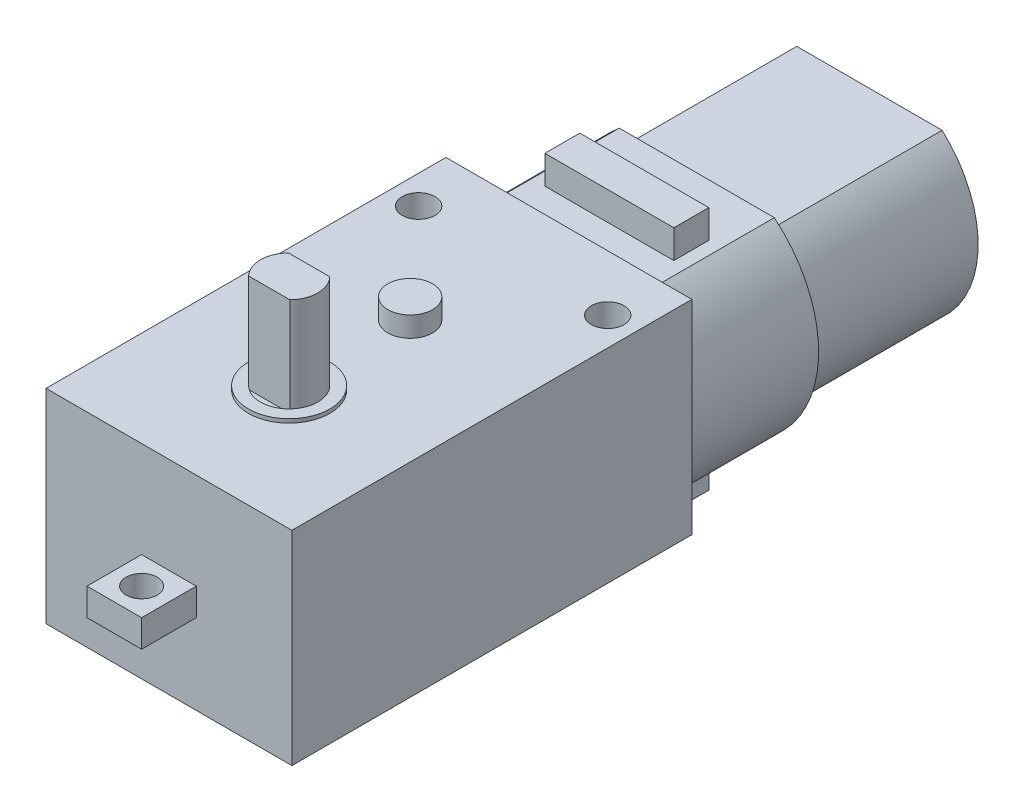
SolidWorks part; units mm, degrees
ref_plane "Front Plane" through (0, 0, 0) normal (0, 0, 1) x (1, 0, 0)
ref_plane "Top Plane" through (0, 0, 0) normal (0, 1, 0) x (1, 0, 0)
ref_plane "Right Plane" through (0, 0, 0) normal (1, 0, 0) x (0, 0, -1)
sketch "Sketch1" plane through (0, 0, 0) normal (0, 1, 0) x (1, 0, 0)
  line L0 (0, -3.725) -> (0, 13.125) construction
  line L1 (-11.25, -11) -> (11.25, -11)
  line L2 (-11.25, -11) -> (-11.25, 25.6)
  line L3 (-11.25, 25.6) -> (11.25, 25.6)
  line L4 (11.25, -11) -> (11.25, 25.6)
  line L5 (-11.25, -11) -> (11.25, 25.6) construction
  line L6 (-11.25, 25.6) -> (11.25, -11) construction
  line L8 (-11.15, 37.3) -> (11.15, 37.3)
  line L9 (-11.15, 37.3) -> (-11.15, 25.6)
  line L10 (-11.15, 25.6) -> (11.15, 25.6)
  line L11 (11.15, 37.3) -> (11.15, 25.6)
  line L12 (-11.15, 37.3) -> (11.15, 25.6) construction
  line L13 (-11.15, 25.6) -> (11.15, 37.3) construction
  line L14 (-9.7, 53.3) -> (9.7, 53.3)
  line L15 (-9.7, 53.3) -> (-9.7, 37.3)
  line L16 (-9.7, 37.3) -> (9.7, 37.3)
  line L17 (9.7, 53.3) -> (9.7, 37.3)
  line L18 (-9.7, 53.3) -> (9.7, 37.3) construction
  line L19 (-9.7, 37.3) -> (9.7, 53.3) construction
  line L26 (-1.8868, -1.825) -> (1.8868, -1.825)
  line L28 (-1.8868, 1.825) -> (1.8868, 1.825)
  line L30 (-1.8868, -1.825) -> (1.8868, 1.825) construction
  line L31 (-1.8868, 1.825) -> (1.8868, -1.825) construction
  circle A0 centre (0, 0) radius 3.725
  circle A1 centre (0, 11.075) radius 2.05
  circle A2 centre (0, 0) radius 2.625
  point P0 (0, 7.3)
  point P12 (0, 31.45)
  point P17 (0, 45.3)
  point P22 (0, 30.9)
  dimension "D3" = 11
  dimension "D4" = 7.45
  dimension "D5" = 16.85
  dimension "D6" = 4.1
  dimension "D14" = 5.25
  dimension "D1" = 36.6
  dimension "D2" = 22.5
  dimension "D7" = 22.3
  dimension "D8" = 19.4
  dimension "D9" = 11.7
  dimension "D10" = 16
  dimension "D15" = 3.65
extrude "Boss-Extrude1" add sketch "Sketch1" against normal blind 18.65 contours L4 L3 L2 L1
ref_plane "Plane2" through (0, -18.65, 0) normal (0, -1, 0) x (-1, 0, 0)
extrude "Boss-Extrude2" add sketch "Sketch1<3>" along normal blind 17.2 from surface contours L8 L11 L10 L9 starting at plane "Plane2"
sketch "Sketch1<3>" plane through (0, 0, 0) normal (0, 1, 0) x (1, 0, 0) same geometry as "Sketch1"
sketch "Sketch3" plane through (0, 0, -25.6) normal (0, 0, -1) x (-1, 0, 0)
  line L0 (11.15, -10.05) -> (-11.15, -10.05) construction
  line L1 (11.15, -1.45) -> (11.15, -18.65) construction
  line L2 (-11.15, -1.45) -> (-11.15, -18.65) construction
  line L3 (11.15, -1.45) -> (-11.15, -1.45) construction
  line L4 (11.15, -18.65) -> (-11.15, -18.65) construction
  line L5 (7.0967, -1.45) -> (-11.15, -1.45)
  line L6 (11.15, -18.65) -> (-11.15, -18.65)
  arc A0 (-7.0967, -18.65) -> (-7.0967, -1.45) centre (0, -10.05) ccw
  arc A1 (7.0967, -1.45) -> (7.0967, -18.65) centre (0, -10.05) ccw
  line M27 (-11.15, -18.65) -> (-11.15, -1.45)
  line M28 (-11.15, -1.45) -> (11.15, -1.45)
  line M29 (11.15, -1.45) -> (11.15, -18.65)
extrude "Cut-Extrude1" cut sketch "Sketch3" along normal up to next contours A0 M29 M28 | A0 L6 M29 | A1 L6 M27 | A1 M28 M27 region at (-9.9842, -3.514, -25.6) region at (9.9842, -3.514, -25.6) region at (-9.9842, -16.586, -25.6) region at (9.9842, -16.586, -25.6)
sketch "Sketch4" plane through (0, 0, -37.3) normal (0, 0, -1) x (-1, 0, 0)
  line L11 (-6.6515, -17.45) -> (6.6515, -17.45)
  line L12 (6.6515, -2.65) -> (-6.6515, -2.65)
  line L13 (-6.6515, -17.45) -> (6.6515, -17.45)
  line L14 (6.6515, -2.65) -> (-6.6515, -2.65)
  arc A7 (-6.6515, -2.65) -> (-6.6515, -17.45) centre (0, -10.05) ccw
  arc A8 (6.6515, -17.45) -> (6.6515, -2.65) centre (0, -10.05) ccw
  arc A9 (-6.6515, -2.65) -> (-6.6515, -17.45) centre (0, -10.05) ccw
  arc A10 (6.6515, -17.45) -> (6.6515, -2.65) centre (0, -10.05) ccw
  dimension "D1" = 1.2
extrude "Boss-Extrude4" add sketch "Sketch4" along normal blind 15.8 contours L13 A10 L14 A9 region at (0, -10.05, -37.3)
sketch "Sketch5" plane through (0, 0, -53.1) normal (0, 0, -1) x (-1, 0, 0)
  line L0 (9.95, -10.05) -> (-9.95, -10.05) construction
  circle A2 centre (0, -10.05) radius 1
  arc A3 (6.6515, -17.45) -> (6.6515, -2.65) centre (0, -10.05) ccw construction
  arc A4 (-6.6515, -2.65) -> (-6.6515, -17.45) centre (0, -10.05) ccw construction
  point P2 (0, 0)
  point P6 (9.95, -10.05)
  point P7 (0, 0)
  point P10 (-6.9256, -10.05)
  point P14 (-9.95, -10.05)
  dimension "D1" = 2
extrude "Boss-Extrude5" add sketch "Sketch5" along normal blind 1.25 contours A2
ref_plane "Plane1" through (0, -10.05, 0) normal (0, 1, 0) x (1, 0, 0)
sketch "Sketch6" plane through (0, 0, 11) normal (0, 0, 1) x (1, 0, 0)
  line L1 (-2.5, -8.8) -> (2.5, -8.8)
  line L2 (-2.5, -8.8) -> (-2.5, -11.3)
  line L3 (-2.5, -11.3) -> (2.5, -11.3)
  line L4 (2.5, -8.8) -> (2.5, -11.3)
  line L5 (-2.5, -8.8) -> (2.5, -11.3) construction
  line L6 (-2.5, -11.3) -> (2.5, -8.8) construction
  point P0 (0, -10.05)
  dimension "D1" = 5
  dimension "D2" = 2.5
extrude "Boss-Extrude6" add sketch "Sketch6" along normal blind 5
sketch "Sketch7" plane through (0, -8.8, 0) normal (0, 1, 0) x (1, 0, 0)
  line L0 (-2.5, -16) -> (-2.5, -11) construction
  line L1 (2.5, -16) -> (-2.5, -16) construction
  circle A0 centre (0, -13.5) radius 1.425
  point P4 (-2.5, -13.5)
  point P7 (0, -16)
  dimension "D1" = 2.85
extrude "Cut-Extrude2" cut sketch "Sketch7" against normal up to next
extrude "Boss-Extrude7" add sketch "Sketch1<5>" along normal blind 0.35 contours A0 A2 region at (-3.6196, 0, 0)
sketch "Sketch1<5>" plane through (0, 0, 0) normal (0, 1, 0) x (1, 0, 0) same geometry as "Sketch1"
extrude "Boss-Extrude8" add sketch "Sketch1<6>" along normal blind 1.85 contours A1 region at (0, 0, -11.075)
sketch "Sketch1<6>" plane through (0, 0, 0) normal (0, 1, 0) x (1, 0, 0) same geometry as "Sketch1"
extrude "Boss-Extrude9" add sketch "Sketch1<7>" along normal blind 9 contours L26 A2 L28 region at (0, 0, 0)
sketch "Sketch1<7>" plane through (0, 0, 0) normal (0, 1, 0) x (1, 0, 0) same geometry as "Sketch1"
sketch "Sketch8" plane through (0, -18.65, 0) normal (0, -1, 0) x (1, 0, 0)
  line L0 (10.15, -20.5) -> (11.25, -20.5) construction
  line L1 (11.25, 11) -> (11.25, -25.6) construction
  line L2 (-10.15, -20.5) -> (-11.25, -20.5) construction
  line L3 (-11.25, 11) -> (-11.25, -25.6) construction
  line L4 (-8.65, -22) -> (-8.65, -25.6) construction
  line L5 (-11.25, -25.6) -> (-7.0967, -25.6) construction
  line L6 (8.65, -22) -> (8.65, -25.6) construction
  line L8 (7.0967, -25.6) -> (11.25, -25.6) construction
  circle A0 centre (8.65, -20.5) radius 1.5
  circle A1 centre (-8.65, -20.5) radius 1.5
  point P18 (0, 0)
  dimension "D2" = 3
  dimension "D1" = 1.1
  dimension "D3" = 3.6
extrude "Cut-Extrude3" cut sketch "Sketch8" against normal up to next
sketch "Sketch10" plane through (0, -1.45, 0) normal (0, 1, 0) x (1, 0, 0)
  line L6 (-7.0967, 37.3) -> (-7.0967, 25.6) construction
  line L7 (7.0967, 37.3) -> (-7.0967, 37.3) construction
  line L8 (-5.9, 32.5) -> (5.9, 32.5)
  line L9 (5.9, 32.5) -> (5.9, 29.3)
  line L10 (-5.9, 29.3) -> (5.9, 29.3)
  line L11 (-5.9, 32.5) -> (-5.9, 29.3)
  dimension "D1" = 11.8
  dimension "D2" = 3.2
  dimension "D3" = 1.1967
  dimension "D4" = 4.8
extrude "Boss-Extrude11" add sketch "Sketch10" along normal blind 2.6
mirror "Mirror5" about plane through (0, -10.05, 0) normal (0, 1, 0) of "Boss-Extrude11"
